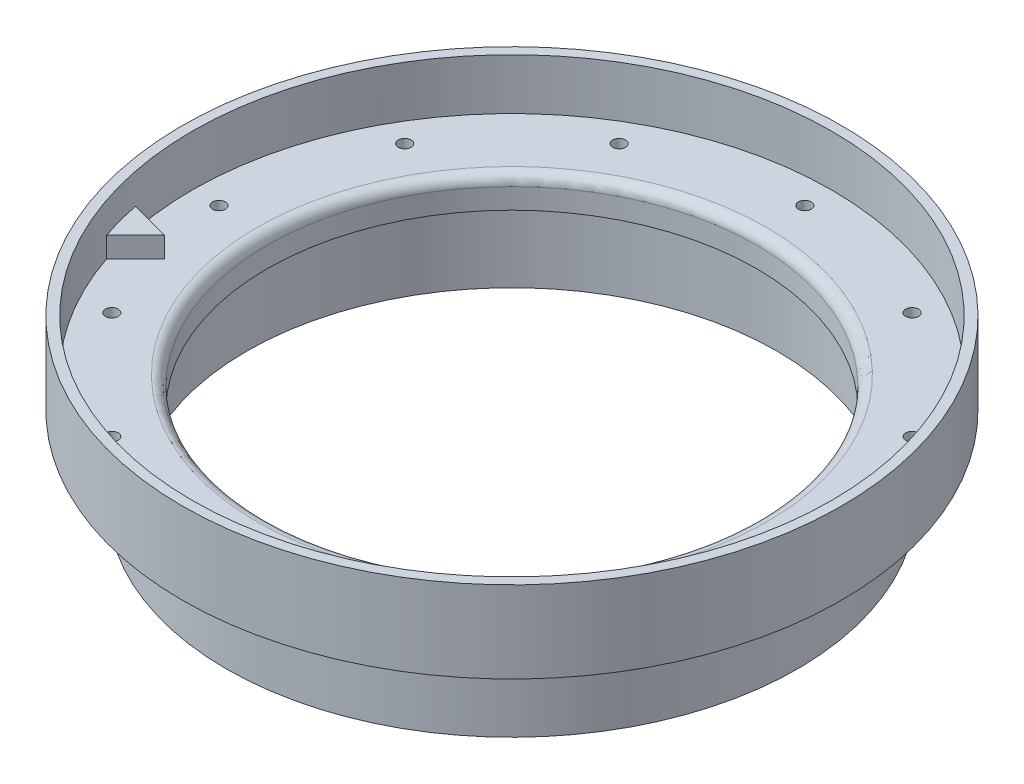
SolidWorks part; units mm, degrees
material "6061-T6 (SS)"
ref_plane "Front Plane" through (0, 0, 0) normal (0, 0, 1) x (1, 0, 0)
ref_plane "Top Plane" through (0, 0, 0) normal (0, 1, 0) x (1, 0, 0)
ref_plane "Right Plane" through (0, 0, 0) normal (1, 0, 0) x (0, 0, -1)
ref_axis "Axis1" through (0, 55, 0) along (0, -1, 0)
sketch "Cross Section" plane through (0, 0, 0) normal (0, 0, 1) x (1, 0, 0)
  line L0 (-38.1, 0) -> (-38.1, -3.175)
  line L1 (-38.1, -3.175) -> (-41.275, -3.175)
  line L2 (-41.275, -3.175) -> (-41.275, -15.875)
  line L4 (0, -15.875) -> (-38.1, -15.875) construction
  line L5 (-44.45, -15.875) -> (-44.45, -3.175)
  line L6 (-44.45, -3.175) -> (-51.308, -3.175)
  line L7 (-51.308, -3.175) -> (-51.308, 9.525)
  line L8 (-51.308, 9.525) -> (-49.784, 9.525)
  line L9 (-49.784, 9.525) -> (-49.784, 1.5875)
  line L11 (-38.1, 0) -> (0, 0) construction
  line L13 (-44.45, -15.875) -> (-41.275, -15.875)
  line L14 (-49.784, 1.5875) -> (-49.784, 3.175) construction
  line L15 (-39.6875, 1.5875) -> (-49.784, 1.5875)
  arc A0 (-39.6875, 1.5875) -> (-38.1, 0) centre (-39.6875, 0) cw
  dimension "D2" = 1.5875
  dimension "D1" = 3.175
  dimension "D3" = 3.175
  dimension "D5" = 6.858
  dimension "D6" = 12.7
  dimension "D9" = 3.175
  dimension "D4" = 1.5875
  dimension "D7" = 38.1
revolve "Main" add sketch "Cross Section" angle 360 about axis through (0, 55, 0) along (0, -1, 0)
sketch "Hole Location" plane through (0, 0, 0) normal (0, 1, 0) x (1, 0, 0)
  line L0 (0, 0) -> (-45.6057, 0) construction
  circle A0 centre (0, 0) radius 45.6057 construction
  dimension "D1" = 91.2114
hole_wizard "#3-48 Tapped Hole1" positions "Sketch1" profile "Sketch2" tap size "#3-48" standard "ANSI Inch" end condition through all
sketch "Sketch1" plane through (0, 1.5875, 0) normal (0, 1, 0) x (1, 0, 0)
  point P0 (-45.6057, 0)
sketch "Sketch2" plane through (-45.6057, 1.5875, 0) normal (1, 0, 0) x (0, 0, 1)
  line L0 (0, 0) -> (0, 17.4625)
  line L1 (0, 17.4625) -> (0.9969, 17.4625)
  line L2 (0.9969, 17.4625) -> (0.9969, 0)
  line L5 (0.9969, 0) -> (0, 0)
  line L11 (0, -6.35) -> (0, 107.95) construction
  dimension "Thru Tap Drill Dia." = 1.9939
  dimension "Thru Tap Drill Depth" = 17.4625
cosmetic thread "Hole Thread1" parameters "D2"=2.5146
pattern_circular "CirPattern1" count 12 over 360 of "#3-48 Tapped Hole1"
sketch "Sketch3" plane through (0, 1.5875, 0) normal (0, 1, 0) x (1, 0, 0)
  line L0 (0, 0) -> (-48.0877, -12.885) construction
  line L1 (0, 0) -> (-45.6057, 0) construction
  line L2 (-47.168, -15.9256) -> (-42.6779, -11.4355)
  line L3 (-42.6779, -11.4355) -> (-48.8115, -9.792)
  circle A0 centre (0, 0) radius 49.784 construction
  circle A1 centre (0, 0) radius 49.784 construction
  arc A2 (-47.168, -15.9256) -> (-48.8115, -9.792) centre (0, 0) cw
  dimension "D1" = 15
  dimension "D2" = 60
  dimension "D3" = 6.35
extrude "Boss-Extrude1" add sketch "Sketch3" along normal blind 3.175
equation "\"D1@Hole Location\"=\"TANK DIAMETER@Cryo Tank.Assembly\"+\"GASKET SEAT THICKNESS@Cryo Tank.Assembly\"+\"LINER THICKNESS@Cryo Tank.Assembly\"+\"SHRINK FIT DELTA@Cryo Tank.Assembly\""
equation "\"D1@Cross Section\"=\"LINER THICKNESS@Cryo Tank.Assembly\""
equation "\"D3@Cross Section\"=\"ALUMINUM LAP THICKNESS@Cryo Tank.Assembly\""
equation "\"D5@Cross Section\"=2*\"CF THICKNESS@Cryo Tank.Assembly\"+\"NOMEX THICKNESS@Cryo Tank.Assembly\""
equation "\"D7@Cross Section\"=\"TANK DIAMETER@Cryo Tank.Assembly\"/2"
